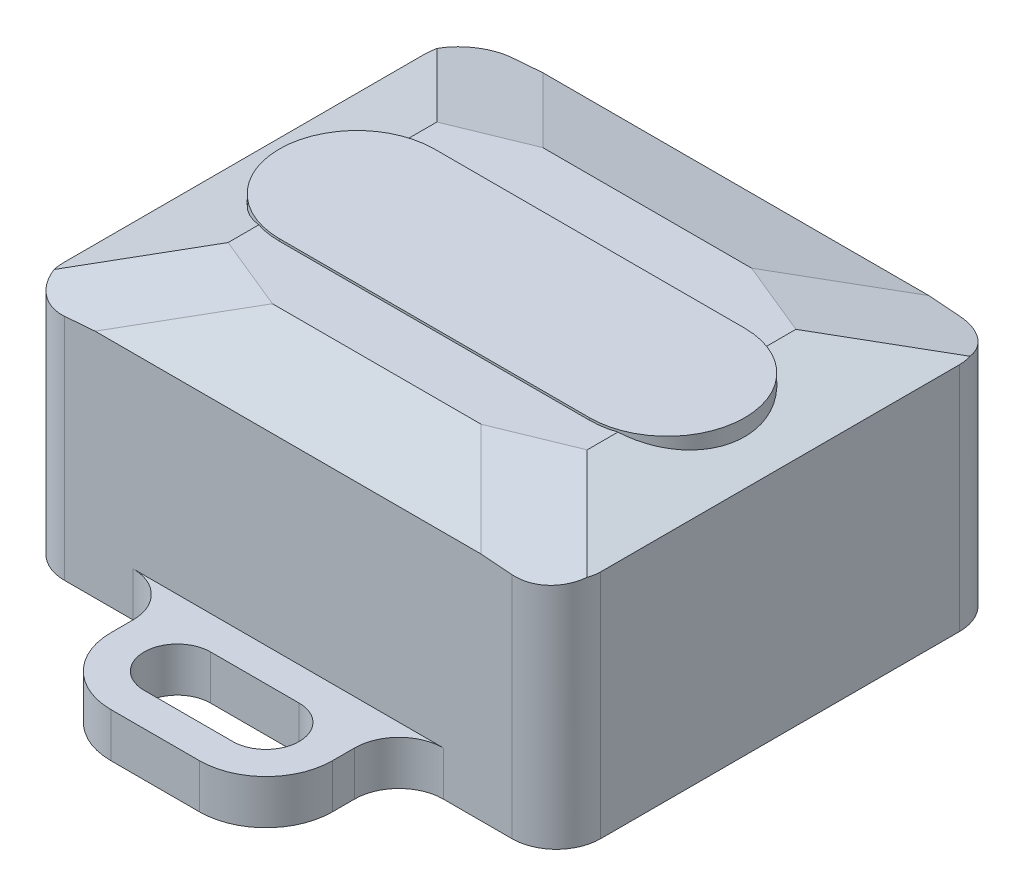
SolidWorks part; units mm, degrees
ref_plane "前视基准面" through (0, 0, 0) normal (0, 0, 1) x (1, 0, 0)
ref_plane "上视基准面" through (0, 0, 0) normal (0, 1, 0) x (1, 0, 0)
ref_plane "右视基准面" through (0, 0, 0) normal (1, 0, 0) x (0, 0, -1)
sketch "草图1" plane through (0, 0, 0) normal (0, 1, 0) x (1, 0, 0)
  line L1 (0, 0) -> (24.2, 0)
  line L2 (0, 0) -> (0, 20.2)
  line L3 (0, 20.2) -> (24.2, 20.2)
  line L4 (24.2, 0) -> (24.2, 20.2)
  dimension "D1" = 24.2
  dimension "D2" = 20.2
extrude "凸台-拉伸1" add sketch "草图1" along normal blind 11.5
sketch "草图2" plane through (0, 0, 0) normal (0, -1, 0) x (1, 0, 0)
  line L0 (0, -10.1) -> (24.2, -10.1) construction
  line L1 (0, -20.2) -> (0, 0) construction
  line L2 (24.2, 0) -> (24.2, -20.2) construction
  line L3 (12.1, -23.2) -> (12.1, 3) construction
  line L4 (14.1, 3) -> (10.1, 3) construction
  line L5 (14.1, 1.5) -> (10.1, 1.5)
  line L6 (14.1, 4.5) -> (10.1, 4.5)
  line L7 (14.1, 3) -> (10.1, 3) construction
  line L8 (17.1, 0) -> (7.1, 0)
  line L9 (14.1, 6) -> (10.1, 6)
  line L10 (17.1, 3) -> (17.1, 0)
  line L11 (0, 0) -> (24.2, 0) construction
  line L12 (7.1, 3) -> (7.1, 0)
  line L13 (14.1, -23.2) -> (10.1, -23.2) construction
  line L14 (7.1, -23.2) -> (7.1, -20.2)
  line L15 (17.1, -23.2) -> (17.1, -20.2)
  line L16 (14.1, -26.2) -> (10.1, -26.2)
  line L17 (17.1, -20.2) -> (7.1, -20.2)
  line L18 (14.1, -23.2) -> (10.1, -23.2) construction
  line L19 (14.1, -21.7) -> (10.1, -21.7)
  line L20 (14.1, -24.7) -> (10.1, -24.7)
  arc A0 (14.1, 1.5) -> (14.1, 4.5) centre (14.1, 3) ccw
  arc A1 (10.1, 4.5) -> (10.1, 1.5) centre (10.1, 3) ccw
  arc A2 (17.1, 3) -> (14.1, 6) centre (14.1, 3) ccw
  arc A3 (10.1, 6) -> (7.1, 3) centre (10.1, 3) ccw
  arc A4 (10.1, -26.2) -> (7.1, -23.2) centre (10.1, -23.2) cw
  arc A5 (17.1, -23.2) -> (14.1, -26.2) centre (14.1, -23.2) cw
  arc A6 (14.1, -21.7) -> (14.1, -24.7) centre (14.1, -23.2) cw
  arc A7 (10.1, -24.7) -> (10.1, -21.7) centre (10.1, -23.2) cw
  point P10 (12.1, 3)
  point P15 (12.1, 3)
  point P33 (12.1, -10.1)
  point P39 (12.1, -23.2)
  point P40 (12.1, -23.2)
  dimension "D1" = 13.1
  dimension "D2" = 3
  dimension "D3" = 4
  dimension "D4" = 16.1
extrude "凸台-拉伸2" add sketch "草图2" against normal blind 2
fillet "圆角1" radius 2 4 edges at (17.1, 1, -20.2) (7.1, 1, -20.2) (7.1, 1, 0) (17.1, 1, 0)
sketch "草图3" plane through (0, 11.5, 0) normal (0, 1, 0) x (1, 0, 0)
  line L0 (0, 10.1) -> (24.2, 10.1) construction
  line L1 (0, 20.2) -> (0, 0) construction
  line L2 (24.2, 0) -> (24.2, 20.2) construction
  line L3 (5.1, 10.1) -> (19.1, 10.1) construction
  line L4 (5.1, 13.6) -> (19.1, 13.6)
  line L5 (5.1, 6.6) -> (19.1, 6.6)
  arc A0 (5.1, 13.6) -> (5.1, 6.6) centre (5.1, 10.1) ccw
  arc A1 (19.1, 6.6) -> (19.1, 13.6) centre (19.1, 10.1) ccw
  point P8 (12.1, 10.1)
  dimension "D1" = 3.5
  dimension "D2" = 14
extrude "凸台-拉伸3" add sketch "草图3" along normal blind 0.1
chamfer "倒角1" distance 4 angle 15 4 edges at (12.1, 11.5, -20.2) (24.2, 11.5, -10.1) (0, 11.5, -10.1) (12.1, 11.5, 0) first distance on face at (12.1, 11.5, -10.1)
chamfer "倒角3" distance 1 angle 15 4 edges at (22.2, 10.9641, -18.2) (2, 10.9641, -18.2) (2, 10.9641, -2) (22.2, 10.9641, -2) first distance on face at (21.9333, 11.0356, -10.1) first distance on face at (2.2667, 11.0356, -10.1)
fillet "圆角2" radius 2 4 edges at (0, 5.082, 0) (0, 5.082, -20.2) (24.2, 5.082, -20.2) (24.2, 5.082, 0)
ref_plane "基准面1" through (12.1, 0, 0) normal (1, 0, 0) x (0, 0, -1)
ref_plane "基准面2" through (0, 0, 3) normal (0, 0, 1) x (1, 0, 0)
ref_plane "基准面3" through (0, 0, -23.2) normal (0, 0, -1) x (-1, 0, 0)
ref_axis "基准轴1" through (12.1, -0.1, 3) along (0, 1, 0)
ref_axis "基准轴2" through (12.1, -0.5214, -23.2) along (0, 1, 0)
